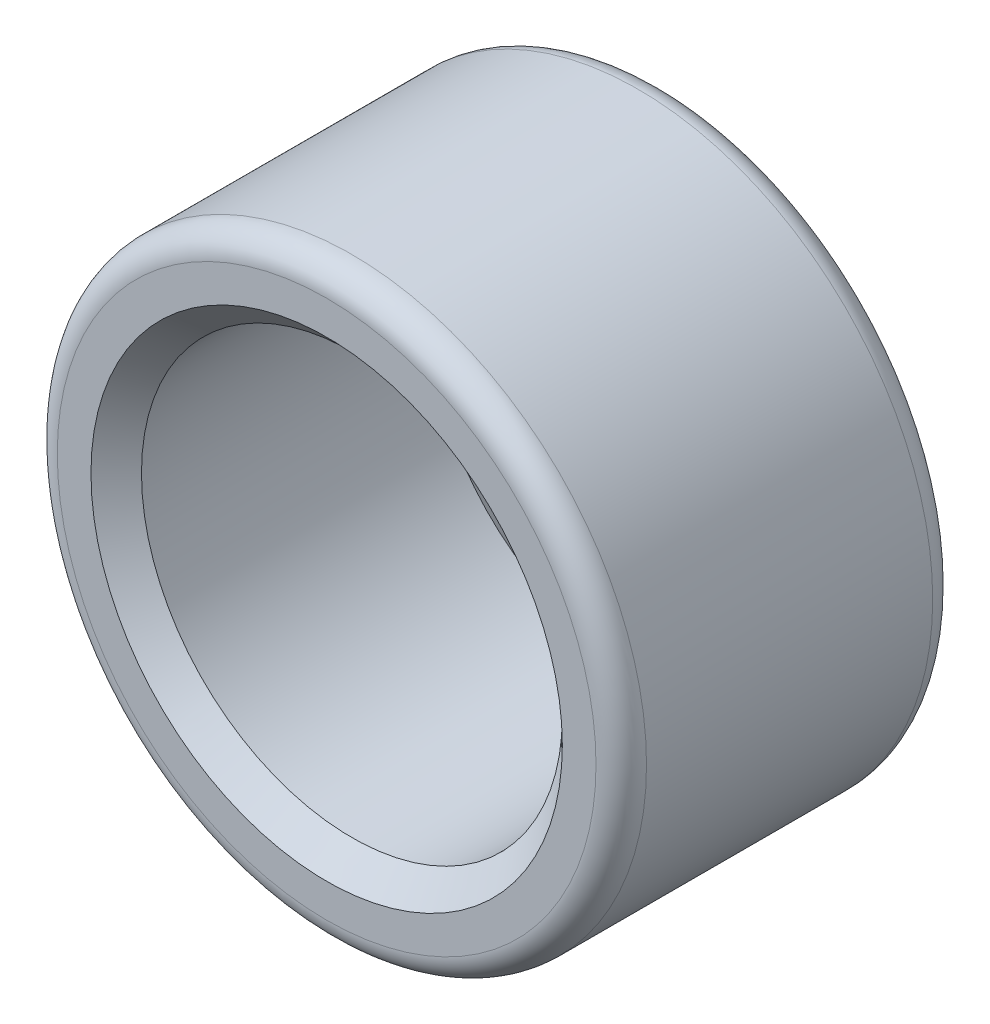
SolidWorks part; units mm, degrees
material "PLA"
ref_plane "Front Plane" through (0, 0, 0) normal (0, 0, 1) x (1, 0, 0)
ref_plane "Top Plane" through (0, 0, 0) normal (0, 1, 0) x (1, 0, 0)
ref_plane "Right Plane" through (0, 0, 0) normal (1, 0, 0) x (0, 0, -1)
sketch "Sketch1" plane through (0, 0, 0) normal (0, 0, 1) x (1, 0, 0)
  circle A0 centre (0, 0) radius 2.5
  circle A1 centre (0, 0) radius 3.5
  dimension "D1" = 5
  dimension "D2" = 1
extrude "Boss-Extrude1" add sketch "Sketch1" along normal mid plane 4
chamfer "Chamfer1" distance 0.3 angle 45 2 edges at (2.5, 0, -2) (2.5, 0, 2)
fillet "Fillet1" radius 0.3 2 edges at (3.5, 0, -2) (3.5, 0, 2)
